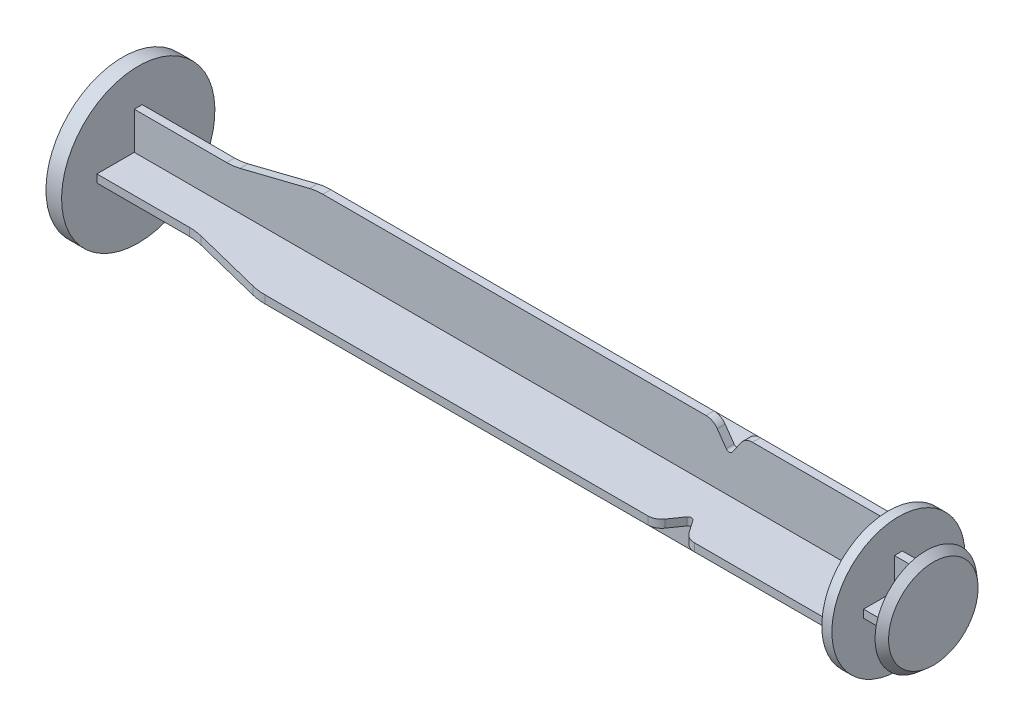
SolidWorks part; units mm, degrees
ref_plane "Front" through (0, 0, 0) normal (0, 0, 1) x (1, 0, 0)
ref_plane "Top" through (0, 0, 0) normal (0, 1, 0) x (1, 0, 0)
ref_plane "Right" through (0, 0, 0) normal (1, 0, 0) x (0, 0, -1)
sketch "Sketch1" plane through (0, 0, 0) normal (0, 0, 1) x (1, 0, 0)
  line L0 (0, 0) -> (84.5, 0)
  line L1 (84.5, 0) -> (84.5, 6.75)
  line L2 (84.5, 6.75) -> (68.25, 6.75)
  line L3 (68.25, 6.75) -> (66.5, 4.25)
  line L4 (66.5, 4.25) -> (64.75, 6.75)
  line L5 (64.75, 6.75) -> (21.5, 6.75)
  line L6 (21.5, 6.75) -> (12.5, 4.5)
  line L7 (12.5, 4.5) -> (0, 4.5)
  line L8 (0, 4.5) -> (0, 0)
  line L9 (66.5, 4.25) -> (66.5, 6.75) construction
  line L10 (66.5, 6.75) -> (68.25, 6.75) construction
  point P3 (0, 3.4063)
  dimension "D1" = 84.5
  dimension "D2" = 2.5
  dimension "D3" = 18
  dimension "D4" = 63
  dimension "D5" = 12.5
  dimension "D6" = 6.75
  dimension "D7" = 3.5
  dimension "D8" = 4.5
extrude "Boss-Extrude1" add sketch "Sketch1" along normal blind 0.43 and the other way blind 0.43
sketch "Sketch2" plane through (0, 0, 0) normal (-1, 0, 0) x (0, 0, 1)
  circle A0 centre (0, 0) radius 8.35
  dimension "D1" = 16.7
extrude "Boss-Extrude2" add sketch "Sketch2" against normal blind 1.7
ref_axis "Axis1" through (1.7, 0, 0) along (1, 0, 0)
pattern_circular "CirPattern1" count 4 over 360 about axis through (1.7, 0, 0) along (1, 0, 0) of "Boss-Extrude1"
sketch "Sketch3" plane through (84.5, 0, 0) normal (1, 0, 0) x (0, 0, -1)
  circle A0 centre (0, 0) radius 7.25
  dimension "D1" = 14.5
extrude "Boss-Extrude3" add sketch "Sketch3" against normal blind 1.1
sketch "Sketch4" plane through (84.5, 0, 0) normal (1, 0, 0) x (0, 0, -1)
  line L0 (0, 0) -> (0, 3.8) construction
  line L1 (0, 0) -> (-3.8, 0) construction
  line L2 (0, 0) -> (0, -3.8) construction
  line L3 (0, 0) -> (3.8, 0) construction
  line L4 (-3.8, -0.43) -> (-3.8, 0.43)
  line L5 (0.43, 3.8) -> (-0.43, 3.8)
  line L6 (0.43, -3.8) -> (-0.43, -3.8)
  line L7 (3.8, -0.43) -> (3.8, 0.43)
  line L8 (-0.43, 3.8) -> (-0.43, 0.43)
  line L9 (-0.43, 0.43) -> (-3.8, 0.43)
  line L10 (-3.8, -0.43) -> (-0.43, -0.43)
  line L11 (-0.43, -0.43) -> (-0.43, -3.8)
  line L12 (0.43, -3.8) -> (0.43, -0.43)
  line L13 (0.43, -0.43) -> (3.8, -0.43)
  line L14 (3.8, 0.43) -> (0.43, 0.43)
  line L15 (0.43, 0.43) -> (0.43, 3.8)
  point P9 (-3.8, 0)
  point P12 (0, 3.8)
  point P15 (0, -3.8)
  point P18 (3.8, 0)
  dimension "D1" = 0.86
  dimension "D2" = 7.6
extrude "Boss-Extrude4" add sketch "Sketch4" along normal blind 3
sketch "Sketch6" plane through (0, 0, 0) normal (0, 1, 0) x (1, 0, 0)
  line L0 (87.5, 0) -> (88.3, 0)
  line L1 (87.5, -0.43) -> (87.5, 0.43) construction
  line L2 (88.3, 0) -> (88.3, -4.875)
  line L3 (88.3, -4.875) -> (87.5, -5.55)
  line L4 (87.5, -5.55) -> (87.5, 0)
  dimension "D1" = 5.55
  dimension "D2" = 4.875
  dimension "D3" = 0.8
revolve "Revolve1" add sketch "Sketch6" angle 360 about L0
fillet "Fillet1" radius 0.4 4 edges at (66.5, 0, -4.25) (66.5, -4.25, 0) (66.5, 0, 4.25) (66.5, 4.25, 0)
fillet "Fillet2" radius 1.5 8 edges at (68.25, 0, -6.75) (64.75, 0, -6.75) (68.25, 6.75, 0) (64.75, 6.75, 0) (64.75, 0, 6.75) (68.25, 0, 6.75) (64.75, -6.75, 0) (68.25, -6.75, 0)
fillet "Fillet3" radius 6 8 edges at (12.5, 4.5, 0) (21.5, 6.75, 0) (12.5, 0, -4.5) (21.5, 0, -6.75) (21.5, -6.75, 0) (12.5, -4.5, 0) (12.5, 0, 4.5) (21.5, 0, 6.75)
